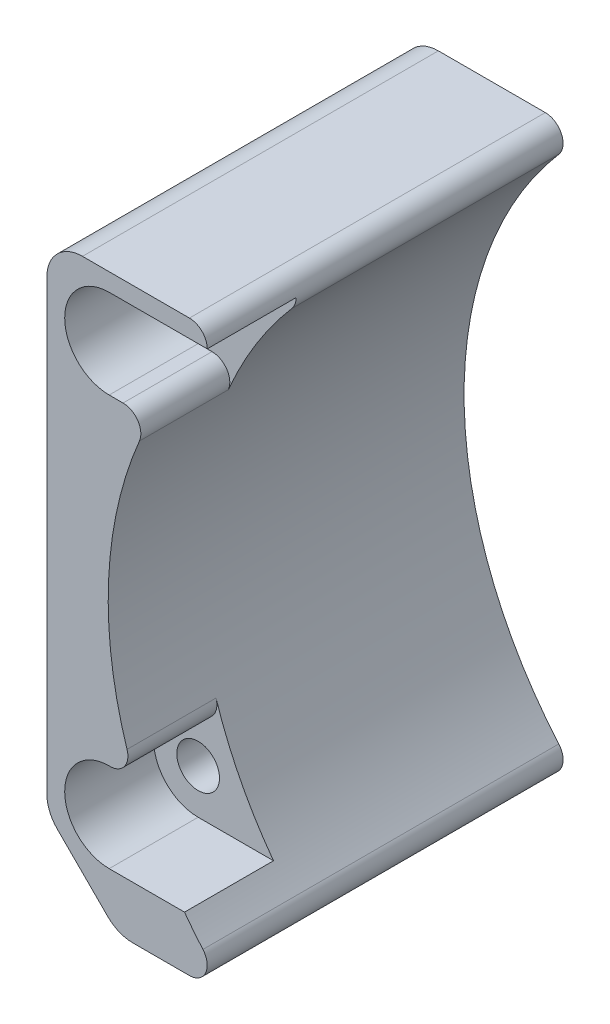
SolidWorks part; units mm, degrees
ref_plane "Front Plane" through (0, 0, 0) normal (0, 0, 1) x (1, 0, 0)
ref_plane "Top Plane" through (0, 0, 0) normal (0, 1, 0) x (1, 0, 0)
ref_plane "Right Plane" through (0, 0, 0) normal (1, 0, 0) x (0, 0, -1)
sketch "Sketch2" plane through (0, 0, 0) normal (0, 0, 1) x (1, 0, 0)
  line L1 (0, 0) -> (16.4239, 0)
  line L2 (0, 0) -> (0, 50.8)
  line L3 (0, 50.8) -> (16.4239, 50.8)
  arc A0 (16.4239, 50.8) -> (16.4239, 0) centre (40.3946, 25.4) ccw
  circle A1 centre (40.3946, 25.4) radius 2.032 construction
  dimension "D2" = 69.85
  dimension "D1" = 50.8
extrude "Boss-Extrude1" add sketch "Sketch2" along normal blind 31.75
chamfer "Chamfer1" distance 6.35 angle 45 1 edges at (0, 0, 15.875)
sketch "Sketch3" plane through (0, 0, 31.75) normal (0, 0, 1) x (1, 0, 0)
  line L0 (16.4239, 50.8) -> (0, 50.8) construction
  line L1 (0, 50.8) -> (0, 6.35) construction
  line L2 (0, 6.35) -> (6.35, 0) construction
  circle A0 centre (5.5562, 45.2438) radius 5.5563 construction
  circle A1 centre (5.5562, 45.2438) radius 1.905
  circle A2 centre (5.5562, 8.6515) radius 5.5562 construction
  circle A3 centre (5.5562, 8.6515) radius 1.905
  dimension "D1" = 11.1125
  dimension "D2" = 3.81
extrude "Cut-Extrude1" cut sketch "Sketch3" against normal through all
fillet "Fillet1" radius 3.175 3 edges at (6.35, 0, 15.875) (0, 6.35, 15.875) (0, 50.8, 15.875)
sketch "Sketch5" [suppressed] plane through (0, 0, 0) normal (0, 0, -1) x (-1, 0, 0)
  line L0 (-5.5562, 49.2125) -> (-13.8302, 49.2125)
  line L1 (-5.5562, 41.275) -> (-8.27, 41.275)
  line L2 (-5.5562, 4.6827) -> (-11.2618, 4.6827)
  line L6 (-5.5563, 12.6202) -> (-6.8757, 12.6202)
  arc A0 (-5.5562, 41.275) -> (-5.5562, 49.2125) centre (-5.5562, 45.2438) ccw
  arc A1 (-15.4078, 0) -> (-15.4078, 50.8) centre (-39.3786, 25.4) ccw construction
  arc A5 (-5.5562, 4.6827) -> (-5.5563, 12.6202) centre (-5.5562, 8.6515) ccw
  arc A7 (-11.2618, 4.6827) -> (-6.8757, 12.6202) centre (-39.3786, 25.4) ccw
  arc A8 (-8.27, 41.275) -> (-13.8302, 49.2125) centre (-39.3786, 25.4) ccw
  dimension "D1" = 7.9375
extrude "Cut-Extrude3" [suppressed] cut sketch "Sketch5" against normal blind 7.9375
sketch "Sketch6" plane through (0, 0, 31.75) normal (0, 0, 1) x (1, 0, 0)
  line L0 (5.5562, 49.2125) -> (14.8462, 49.2125)
  line L1 (5.5562, 41.275) -> (9.2861, 41.275)
  line L2 (5.5562, 12.6202) -> (7.8918, 12.6202)
  line L3 (5.5562, 4.6827) -> (12.2779, 4.6827)
  arc A0 (5.5562, 49.2125) -> (5.5562, 41.275) centre (5.5562, 45.2438) ccw
  arc A1 (5.5562, 12.6202) -> (5.5562, 4.6827) centre (5.5562, 8.6515) ccw
  arc A2 (16.4239, 50.8) -> (16.4239, 0) centre (40.3946, 25.4) ccw construction
  arc A3 (14.8462, 49.2125) -> (9.2861, 41.275) centre (40.3946, 25.4) ccw
  arc A4 (7.8918, 12.6202) -> (12.2779, 4.6827) centre (40.3946, 25.4) ccw
  dimension "D1" = 7.9375
extrude "Cut-Extrude4" cut sketch "Sketch6" against normal blind 7.9375
fillet "Fillet3" radius 1.5875 2 edges at (16.4239, 0, 15.875) (16.4239, 50.8, 15.875)
fillet "Fillet4" [suppressed] radius 1.5875
fillet "Fillet5" radius 1.5875 2 edges at (7.8918, 12.6202, 27.7812) (9.2861, 41.275, 27.7812)
